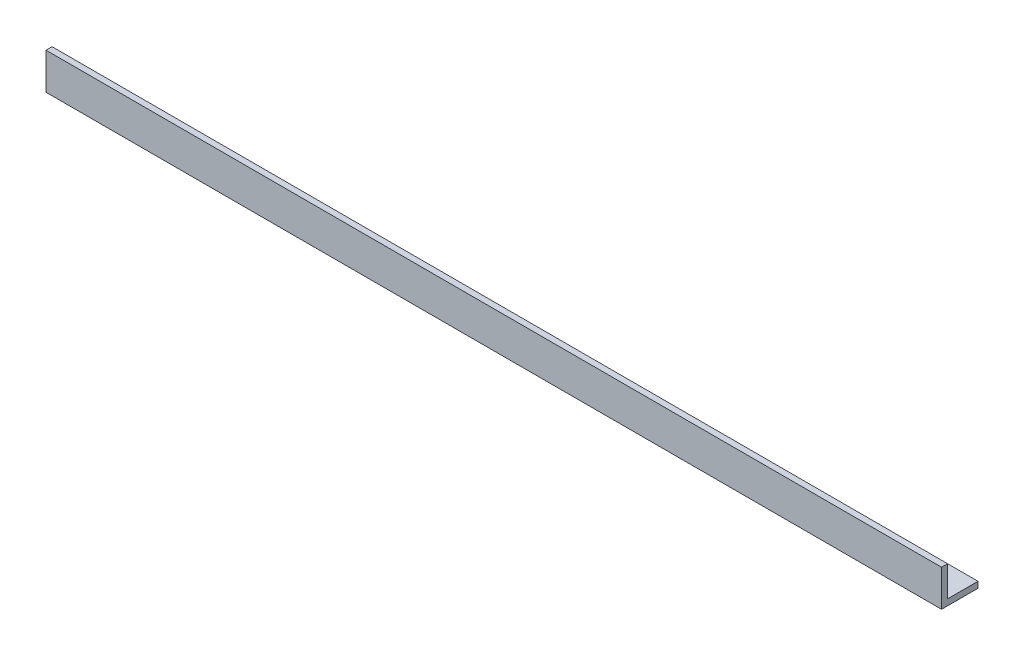
SolidWorks part; units mm, degrees
ref_plane "Front Plane" through (0, 0, 0) normal (0, 0, 1) x (1, 0, 0)
ref_plane "Top Plane" through (0, 0, 0) normal (0, 1, 0) x (1, 0, 0)
ref_plane "Right Plane" through (0, 0, 0) normal (1, 0, 0) x (0, 0, -1)
sketch "Sketch1" plane through (0, 0, 0) normal (1, 0, 0) x (0, 0, -1)
  line L0 (0, 0) -> (0, 19.05)
  line L1 (0, 19.05) -> (3.175, 19.05)
  line L2 (3.175, 19.05) -> (3.175, 3.175)
  line L3 (3.175, 3.175) -> (19.05, 3.175)
  line L4 (19.05, 3.175) -> (19.05, 0)
  line L5 (19.05, 0) -> (0, 0)
extrude "Boss-Extrude1" add sketch "Sketch1" against normal blind 468
sketch "Sketch2" plane through (0, 3.175, 0) normal (0, 1, 0) x (1, 0, 0)
  circle A0 centre (-21.13, 11.2735) radius 6
  circle A1 centre (-56.88, 11.2735) radius 6
  circle A2 centre (-92.63, 11.2735) radius 6
  circle A3 centre (-128.38, 11.2735) radius 6
  circle A4 centre (-164.13, 11.2735) radius 6
  circle A5 centre (-199.88, 11.2735) radius 6
  circle A6 centre (-235.63, 11.2735) radius 6
  circle A7 centre (-271.38, 11.2735) radius 6
  circle A8 centre (-307.13, 11.2735) radius 6
  circle A9 centre (-342.88, 11.2735) radius 6
  circle A10 centre (-378.63, 11.2735) radius 6
  circle A11 centre (-414.38, 11.2735) radius 6
  circle A12 centre (-450.13, 11.2735) radius 6
extrude "Cut-Extrude1" cut sketch "Sketch2" against normal blind 3.175
